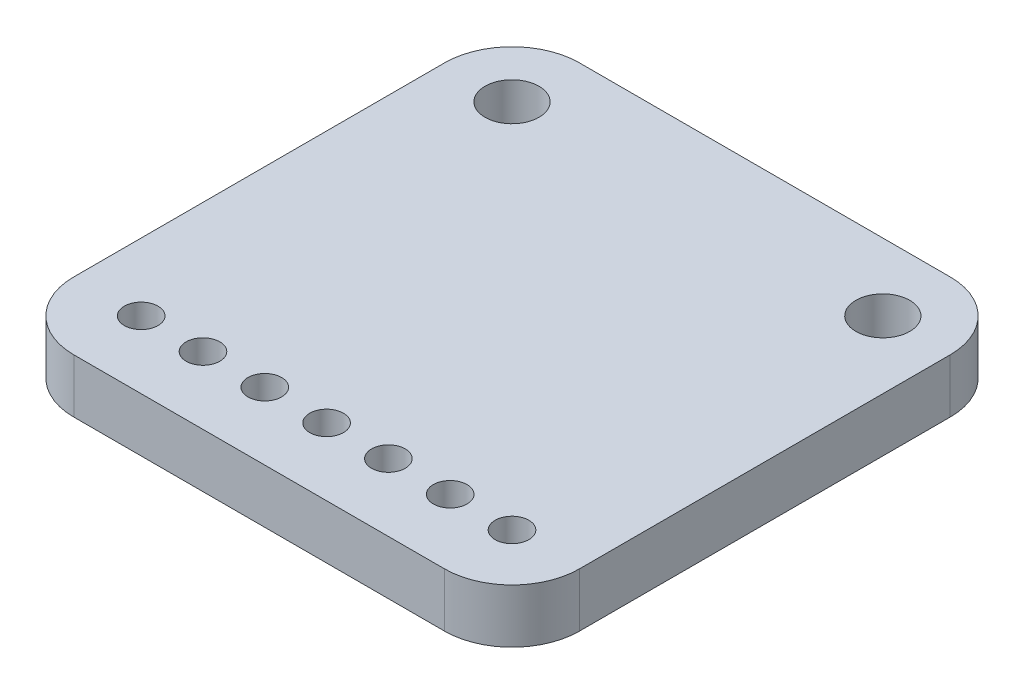
SolidWorks part; units mm, degrees
ref_plane "Front Plane" through (0, 0, 0) normal (0, 0, 1) x (1, 0, 0)
ref_plane "Top Plane" through (0, 0, 0) normal (0, 1, 0) x (1, 0, 0)
ref_plane "Right Plane" through (0, 0, 0) normal (1, 0, 0) x (0, 0, -1)
sketch "Sketch1" plane through (0, 0, 0) normal (0, 1, 0) x (1, 0, 0)
  line L0 (0, 2.54) -> (0, 16.51)
  line L1 (2.54, 19.05) -> (16.51, 19.05)
  line L2 (19.05, 16.51) -> (19.05, 2.54)
  line L3 (16.51, 0) -> (2.54, 0)
  arc A0 (0, 16.51) -> (2.54, 19.05) centre (2.54, 16.51) cw
  arc A1 (16.51, 19.05) -> (19.05, 16.51) centre (16.51, 16.51) cw
  arc A2 (19.05, 2.54) -> (16.51, 0) centre (16.51, 2.54) cw
  arc A3 (0, 2.54) -> (2.54, 0) centre (2.54, 2.54) ccw
  point P13 (0, 0)
  dimension "D1" = 2.54
  dimension "D2" = 19.05
  dimension "D3" = 19.05
extrude "Boss-Extrude1" add sketch "Sketch1" along normal blind 2.032
sketch "Sketch2" plane through (0, 2.032, 0) normal (0, 1, 0) x (1, 0, 0)
  line L0 (2.54, 16.51) -> (16.51, 16.51) construction
  line L1 (16.51, 19.05) -> (2.54, 19.05) construction
  line L2 (2.54, 0) -> (16.51, 0) construction
  line L3 (2.54, 2.54) -> (4.8683, 2.54) construction
  line L4 (4.8683, 2.54) -> (7.1967, 2.54) construction
  line L5 (7.1967, 2.54) -> (9.525, 2.54) construction
  line L6 (9.525, 2.54) -> (11.8533, 2.54) construction
  line L7 (11.8533, 2.54) -> (14.1817, 2.54) construction
  line L8 (14.1817, 2.54) -> (16.51, 2.54) construction
  circle A0 centre (2.54, 16.51) radius 1.016
  circle A1 centre (16.51, 16.51) radius 1.016
  circle A4 centre (2.54, 2.54) radius 0.635
  circle A5 centre (4.8683, 2.54) radius 0.635
  circle A6 centre (7.1967, 2.54) radius 0.635
  circle A7 centre (9.525, 2.54) radius 0.635
  circle A8 centre (11.8533, 2.54) radius 0.635
  circle A9 centre (14.1817, 2.54) radius 0.635
  circle A10 centre (16.51, 2.54) radius 0.635
  point P4 (9.525, 19.05)
  point P7 (9.525, 16.51)
  point P12 (1.4686, 2.977)
  point P25 (9.525, 0)
  point P27 (1.5562, 2.54)
  point P28 (2.1257, 2.54)
  point P29 (0, 0)
  dimension "D2" = 2.032
  dimension "D5" = 1.27
  dimension "D1" = 13.97
  dimension "D3" = 16.51
  dimension "D4" = 2.54
extrude "Cut-Extrude1" cut sketch "Sketch2" against normal through all
